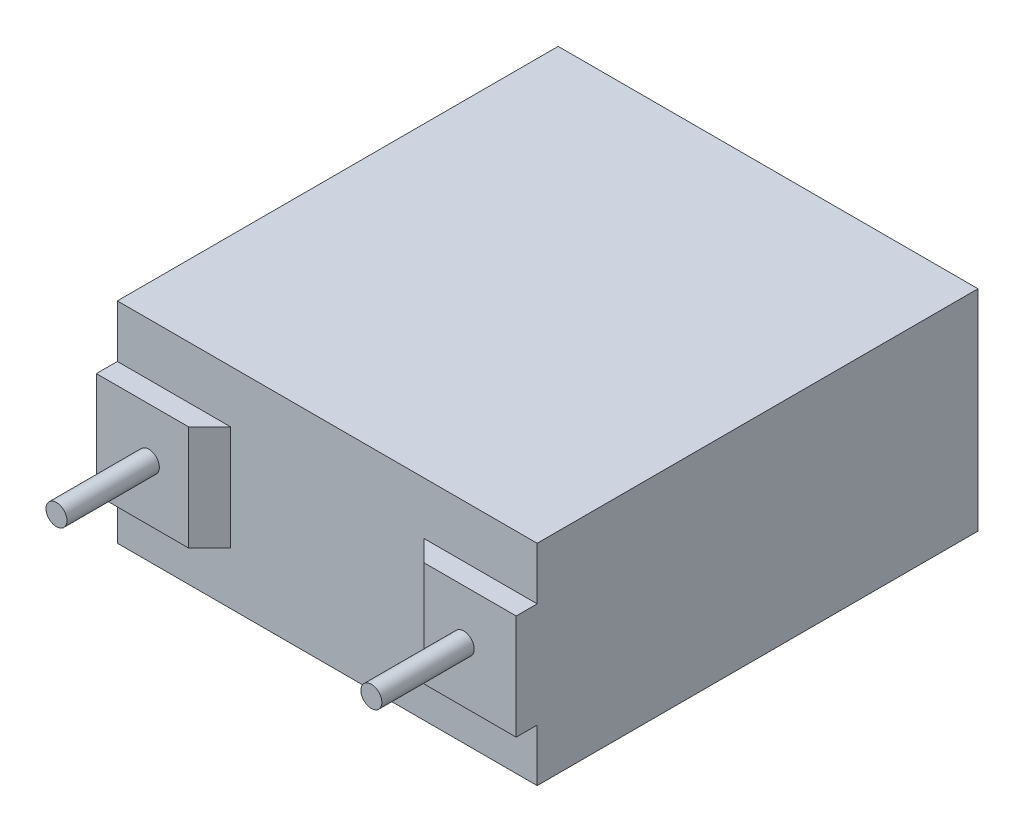
SolidWorks part; units mm, degrees
ref_plane "Front Plane" through (0, 0, 0) normal (0, 0, 1) x (1, 0, 0)
ref_plane "Top Plane" through (0, 0, 0) normal (0, 1, 0) x (1, 0, 0)
ref_plane "Right Plane" through (0, 0, 0) normal (1, 0, 0) x (0, 0, -1)
sketch "Sketch1" plane through (0, 0, 0) normal (0, 0, 1) x (1, 0, 0)
  line L1 (-5, 2.5) -> (5, 2.5)
  line L2 (-5, 2.5) -> (-5, -2.5)
  line L3 (-5, -2.5) -> (5, -2.5)
  line L4 (5, 2.5) -> (5, -2.5)
  point P4 (0, -2.5)
  point P6 (-5, 0)
  dimension "D1" = 10
  dimension "D2" = 5
sketch "Sketch2" plane through (0, 0, 0) normal (0, 0, 1) x (1, 0, 0)
  line L0 (-5, 2.5) -> (-5, -2.5) construction
  line L1 (-5, 1.25) -> (-2.8, 1.25)
  line L2 (-5, 1.25) -> (-5, -1.25)
  line L3 (-5, -1.25) -> (-2.8, -1.25)
  line L4 (-2.8, 1.25) -> (-2.8, -1.25)
  line L5 (0, 2.5) -> (0, -2.5) construction
  line L6 (-5, 2.5) -> (5, 2.5) construction
  line L7 (-5, -2.5) -> (5, -2.5) construction
  line L8 (5, -1.25) -> (2.8, -1.25)
  line L9 (5, 1.25) -> (5, -1.25)
  line L10 (5, 1.25) -> (2.8, 1.25)
  line L11 (2.8, 1.25) -> (2.8, -1.25)
  point P6 (-2.8, 0)
  dimension "D1" = 2.2
  dimension "D2" = 2.5
extrude "Boss-Extrude1" add sketch "Sketch1" against normal blind 10.5
extrude "Boss-Extrude2" add sketch "Sketch2" along normal blind 0.5
chamfer "Chamfer1" distance 0.5 angle 45 2 edges at (2.8, 0, 0) (-2.8, 0, 0)
sketch "Sketch4" plane through (0, 0, 0.5) normal (0, 0, 1) x (1, 0, 0)
  line L0 (0, 0.8344) -> (0, -0.5715) construction
  circle A0 centre (-3.75, 0.0659) radius 0.25
  circle A1 centre (3.75, 0.0659) radius 0.25
  dimension "D1" = 0.5
  dimension "D2" = 7.5
extrude "Boss-Extrude3" add sketch "Sketch4" along normal blind 2.2
